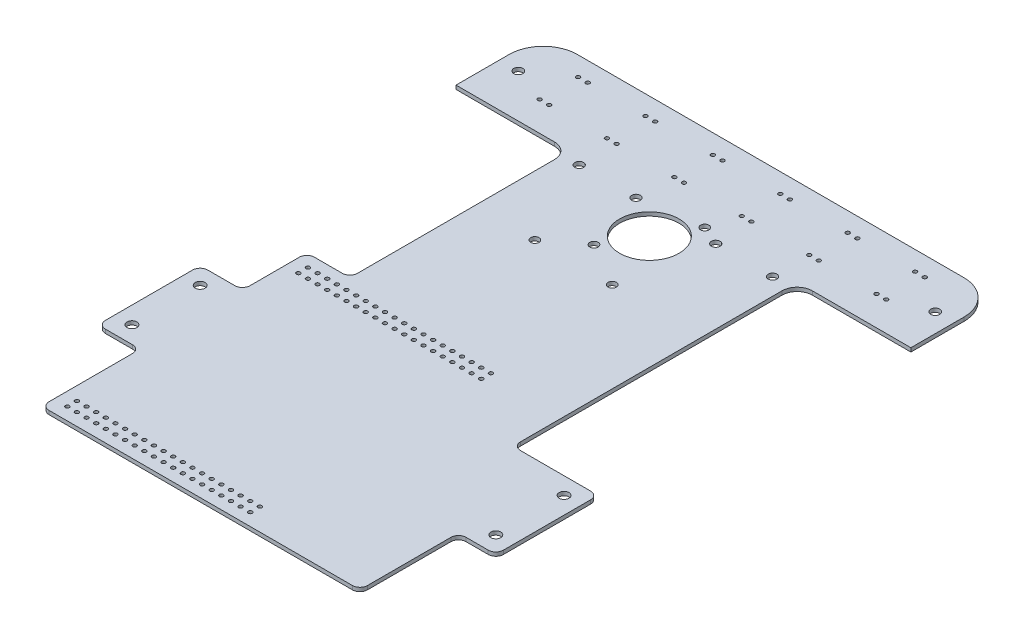
SolidWorks part; units mm, degrees
material "Thornel VCB-20 Carbon Cloth"
ref_plane "Front" through (0, 0, 0) normal (0, 0, 1) x (1, 0, 0)
ref_plane "Top" through (0, 0, 0) normal (0, 1, 0) x (1, 0, 0)
ref_plane "Right" through (0, 0, 0) normal (1, 0, 0) x (0, 0, -1)
ref_axis "X" through (-80.9, 0, 0) along (1, 0, 0)
ref_axis "Y" through (0, -50, 0) along (0, 1, 0)
ref_axis "Z" through (0, 0, -80.9) along (0, 0, 1)
sketch "Sketch1" plane through (0, 0, 0) normal (0, 1, 0) x (1, 0, 0)
  line L0 (-52.5, -125) -> (-41.35, -125)
  line L1 (-52.5, -125) -> (-52.5, -98)
  line L2 (-52.5, -98) -> (-41.35, -98)
  line L3 (-30, -81) -> (-30, -23)
  line L4 (-30, -23) -> (-60, -23)
  line L5 (-60, -23) -> (-60, 0)
  line L6 (-60, 0) -> (60, 0)
  line L7 (60, 0) -> (60, -23)
  line L8 (60, -23) -> (30, -23)
  line L9 (30, -23) -> (30, -98)
  line L10 (30, -98) -> (52.5, -98)
  line L11 (52.5, -98) -> (52.5, -125)
  line L12 (0, -162) -> (0, 0) construction
  line L13 (-41.35, -125) -> (-41.35, -151)
  line L14 (-41.35, -151) -> (42.65, -151)
  line L15 (42.65, -151) -> (42.65, -125)
  line L16 (42.65, -125) -> (52.5, -125)
  line L18 (-41.35, -98) -> (-41.35, -81)
  line L19 (-41.35, -81) -> (-30, -81)
  dimension "D1" = 105
  dimension "D2" = 60
  dimension "D3" = 27
  dimension "D4" = 90
  dimension "D5" = 23
  dimension "D6" = 120
  dimension "D7" = 125
  dimension "D8" = 41.35
  dimension "D9" = 26
  dimension "D10" = 42.65
  dimension "D11" = 17
extrude "Boss-Extrude1" add sketch "Sketch1" along normal mid plane 1
hole_wizard "M2 Clearance Hole1" positions "Sketch2" profile "Sketch3" hole size "M2" standard "ANSI Metric" end condition up to next
sketch "Sketch2" plane through (0, 0.5, 0) normal (0, 1, 0) x (1, 0, 0)
  line L0 (-48, -120.5) -> (48, -120.5) construction
  line L2 (-52.5, -125) -> (-41.35, -125) construction
  line L3 (-52.5, -98) -> (-52.5, -125) construction
  line L4 (52.5, -125) -> (52.5, -98) construction
  line L5 (-48, -102.5) -> (-48, -120.5) construction
  line L8 (48, -102.5) -> (48, -120.5) construction
  point P0 (-48, -120.5)
  point P2 (48, -120.5)
  point P15 (-48, -102.5)
  point P17 (48, -102.5)
  dimension "D1" = 4.5
  dimension "D2" = 4.5
  dimension "D3" = 4.5
  dimension "D4" = 18
sketch "Sketch3" plane through (-48, 0.5, 120.5) normal (1, 0, 0) x (0, 0, 1)
  line L0 (0, 0) -> (0, 1)
  line L1 (0, 1) -> (1.3, 1)
  line L2 (1.3, 1) -> (1.3, 0)
  line L5 (1.3, 0) -> (0, 0)
  line L11 (0, -6.35) -> (0, 107.95) construction
  dimension "Thru Hole Dia." = 2.6
  dimension "Thru Hole Depth" = 1
fillet "Fillet1" radius 2 7 edges at (-52.5, 0, 125) (52.5, 0, 98) (-52.5, 0, 98) (-41.35, 0, 151) (42.65, 0, 151) (52.5, 0, 125) (-41.35, 0, 81)
fillet "Fillet2" radius 9 2 edges at (60, 0, 0) (-60, 0, 0)
hole_wizard "M2 Clearance Hole2" positions "Sketch7" profile "Sketch8" hole size "M2" standard "ANSI Metric" end condition up to next
sketch "Sketch7" plane through (0, 0.5, 0) normal (0, 1, 0) x (1, 0, 0)
  line L0 (-55, -11.57) -> (55, -11.57) construction
  line L2 (0, 0) -> (0, -11.57) construction
  line L3 (51, 0) -> (-51, 0) construction
  line L5 (-60, -23) -> (-30, -23) construction
  point P0 (-55, -11.57)
  point P2 (55, -11.57)
  dimension "D1" = 110
  dimension "D2" = 11.43
sketch "Sketch8" plane through (-55, 0.5, 11.57) normal (1, 0, 0) x (0, 0, 1)
  line L0 (0, 0) -> (0, 1)
  line L1 (0, 1) -> (1.2, 1)
  line L2 (1.2, 1) -> (1.2, 0)
  line L5 (1.2, 0) -> (0, 0)
  line L11 (0, -6.35) -> (0, 107.95) construction
  dimension "Thru Hole Dia." = 2.4
  dimension "Thru Hole Depth" = 1
fillet "Fillet4" radius 2 5 edges at (30, 0, 98) (42.65, 0, 125) (-41.35, 0, 125) (-30, 0, 81) (-41.35, 0, 98)
fillet "Fillet5" radius 4 2 edges at (30, 0, 23) (-30, 0, 23)
sketch "Sketch13" plane through (0, 0.5, 0) normal (0, 1, 0) x (1, 0, 0)
  line L0 (-38, -106) -> (-38, -117) construction
  line L1 (-35, -106) -> (-35, -117)
  line L3 (38, -106) -> (38, -117) construction
  line L5 (35, -106) -> (35, -117)
  line L6 (-38, -111.5) -> (38, -111.5) construction
  line L7 (0, -111.5) -> (0, 0) construction
  line L8 (51, 0) -> (-51, 0) construction
  line L11 (-48, -102.5) -> (-48, -120.5) construction
  line L12 (-48, -111.5) -> (-38, -111.5) construction
  line L13 (-38, -103) -> (-45.5, -103)
  line L14 (-38, -120) -> (-45.5, -120)
  line L15 (38, -103) -> (45.5, -103)
  line L16 (38, -120) -> (45.5, -120)
  line L17 (48.5, -106) -> (48.5, -117)
  line L18 (-48.5, -106) -> (-48.5, -117)
  line L19 (-35, -111.5) -> (-48.5, -111.5) construction
  line L20 (35, -111.5) -> (48.5, -111.5) construction
  arc A0 (-35, -106) -> (-38, -103) centre (-38, -106) ccw
  arc A1 (-38, -120) -> (-35, -117) centre (-38, -117) ccw
  arc A2 (38, -103) -> (35, -106) centre (38, -106) ccw
  arc A3 (35, -117) -> (38, -120) centre (38, -117) ccw
  circle A4 centre (-48, -102.5) radius 1.3 construction
  arc A5 (45.5, -103) -> (48.5, -106) centre (45.5, -106) cw
  arc A6 (48.5, -117) -> (45.5, -120) centre (45.5, -117) cw
  arc A7 (-45.5, -103) -> (-48.5, -106) centre (-45.5, -106) ccw
  arc A8 (-48.5, -117) -> (-45.5, -120) centre (-45.5, -117) ccw
  point P2 (-38, -111.5)
  point P8 (38, -111.5)
  dimension "D5" = 3.5
  dimension "D1" = 17
  dimension "D2" = 13.5
  dimension "D3" = 70
extrude "Cut-Extrude4" [suppressed] cut sketch "Sketch13" against normal through all
hole_wizard "M2 Clearance Hole3" positions "Sketch14" profile "Sketch15" hole size "M2" standard "ANSI Metric" end condition up to next
sketch "Sketch14" plane through (0, 0.5, 0) normal (0, 1, 0) x (1, 0, 0)
  line L2 (5.35, -22.7335) -> (-5.35, -41.2665) construction
  line L3 (0, 0) -> (0, -32) construction
  line L4 (51, 0) -> (-51, 0) construction
  point P0 (5.35, -22.7335)
  point P2 (-5.35, -41.2665)
  dimension "D1" = 21.4
  dimension "D2" = 32
  dimension "D3" = 30
sketch "Sketch15" plane through (5.35, 0.5, 22.7335) normal (1, 0, 0) x (0, 0, 1)
  line L0 (0, 0) -> (0, 1)
  line L1 (0, 1) -> (1.1, 1)
  line L2 (1.1, 1) -> (1.1, 0)
  line L5 (1.1, 0) -> (0, 0)
  line L11 (0, -6.35) -> (0, 107.95) construction
  dimension "Thru Hole Dia." = 2.2
  dimension "Thru Hole Depth" = 1
sketch "Sketch17" plane through (0, 0.5, 0) normal (0, 1, 0) x (1, 0, 0)
  line L0 (-25.5, -25) -> (-10.5, -25) construction
  line L1 (-10.5, -25) -> (10.5, -25) construction
  line L2 (10.5, -25) -> (25.5, -25) construction
  line L4 (0, -25) -> (0, 0) construction
  line L5 (-18, -25) -> (-18, -29.652) construction
  line L7 (51, 0) -> (-51, 0) construction
  line L8 (18, -25) -> (18, -28.4507) construction
  circle A8 centre (25.5, -25) radius 1.15
  circle A9 centre (10.5, -25) radius 1.15
  circle A10 centre (-10.5, -25) radius 1.15
  circle A11 centre (-25.5, -25) radius 1.15
  dimension "D7" = 2.3
  dimension "D1" = 15
  dimension "D2" = 36
  dimension "D4" = 25
extrude "Cut-Extrude6" cut sketch "Sketch17" against normal through all
sketch "Sketch18" plane through (0, 0.5, 0) normal (0, 1, 0) x (1, 0, 0)
  line L0 (5.35, -22.7335) -> (-5.35, -41.2665) construction
  circle A0 centre (0, -32) radius 7.85
  circle A6 centre (5.35, -22.7335) radius 1.1 construction
  circle A8 centre (-5.35, -41.2665) radius 1.1 construction
  dimension "D3" = 15.7
extrude "Cut-Extrude7" cut sketch "Sketch18" against normal up to next
hole_wizard "M2 Clearance Hole4" positions "Sketch19" profile "Sketch20" hole size "M2" standard "ANSI Metric" end condition up to next
sketch "Sketch19" plane through (0, 0.5, 0) normal (0, 1, 0) x (1, 0, 0)
  line L0 (-14.21, -48) -> (6.21, -48) construction
  line L2 (0, 0) -> (0, -48) construction
  line L3 (51, 0) -> (-51, 0) construction
  point P0 (-14.21, -48)
  point P2 (6.21, -48)
  dimension "D1" = 20.42
  dimension "D2" = 6.21
  dimension "D3" = 48
sketch "Sketch20" plane through (-14.21, 0.5, 48) normal (1, 0, 0) x (0, 0, 1)
  line L0 (0, 0) -> (0, 1)
  line L1 (0, 1) -> (1.1, 1)
  line L2 (1.1, 1) -> (1.1, 0)
  line L5 (1.1, 0) -> (0, 0)
  line L11 (0, -6.35) -> (0, 107.95) construction
  dimension "Thru Hole Dia." = 2.2
  dimension "Thru Hole Depth" = 1
sketch "Sketch21" plane through (0, 0.5, 0) normal (0, 1, 0) x (1, 0, 0)
  line L0 (-37.826, -86.7798) -> (-37.826, -147.73) construction
  line L4 (-39.35, -151) -> (40.65, -151) construction
  line L5 (-41.35, -127) -> (-41.35, -149) construction
  circle A0 centre (-37.826, -147.73) radius 0.51
  circle A2 centre (-37.826, -86.7798) radius 0.51
  point P6 (-38.0038, -147.73)
  dimension "D2" = 1.02
  dimension "D3" = 3.524
  dimension "D4" = 3.27
  dimension "D1" = 60.9502
extrude "Cut-Extrude8" cut sketch "Sketch21" against normal up to next
pattern_linear "LPattern1" count 2 spacing 2.54 along (0, 0, -1) count 20 spacing 2.54 along (1, 0, 0) of "Cut-Extrude8"
sketch "Sketch22" plane through (0, 0.5, 0) normal (0, 1, 0) x (1, 0, 0)
  line L0 (-45.72, -5.08) -> (-43.18, -5.08) construction
  line L1 (51, 0) -> (-51, 0) construction
  line L2 (-44.45, -5.08) -> (-44.45, 0) construction
  circle A0 centre (-45.72, -5.08) radius 0.51
  circle A1 centre (-43.18, -5.08) radius 0.51
  point P8 (0, 0)
  dimension "D2" = 1.02
  dimension "D1" = 2.54
  dimension "D3" = 5.08
  dimension "D4" = 44.45
extrude "Cut-Extrude9" cut sketch "Sketch22" against normal up to next
pattern_linear "LPattern2" count 2 spacing 10.16 along (0, 0, 1) count 6 spacing 17.78 along (1, 0, 0) of "Cut-Extrude9"
equation "\"dd\"=4"
